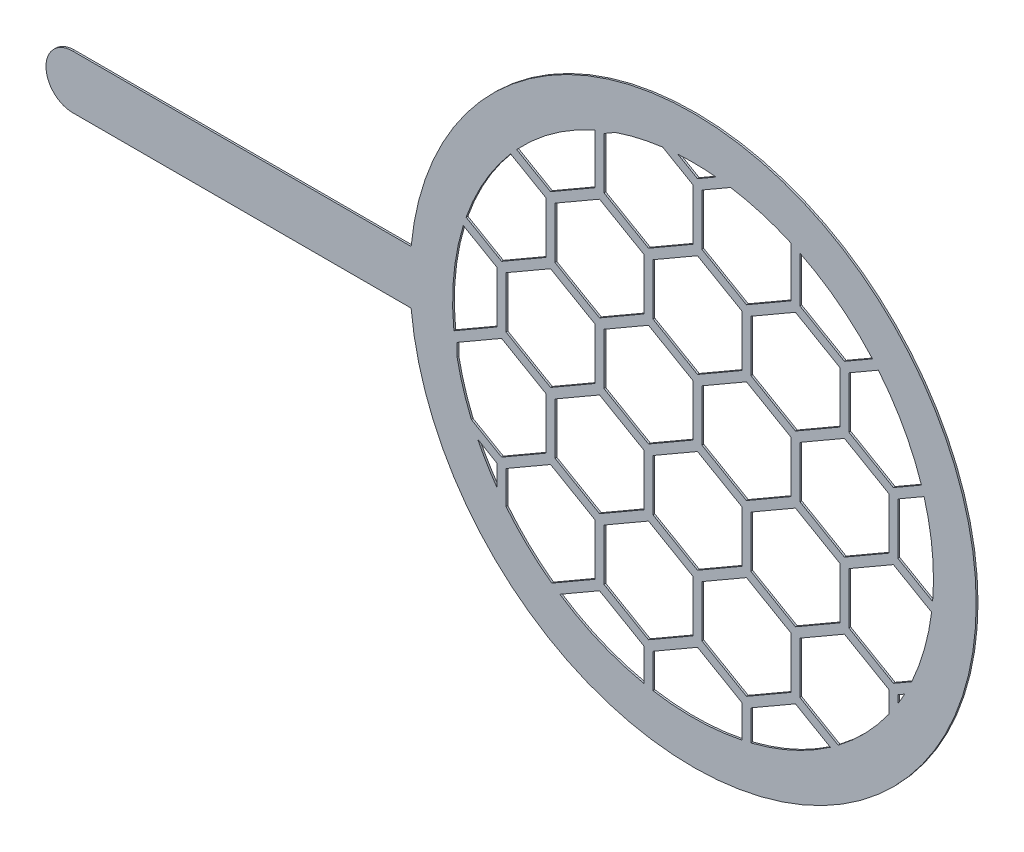
SolidWorks part; units mm, degrees
ref_plane "Plan de face" through (0, 0, 0) normal (0, 0, 1) x (1, 0, 0)
ref_plane "Plan de dessus" through (0, 0, 0) normal (0, 1, 0) x (1, 0, 0)
ref_plane "Plan de droite" through (0, 0, 0) normal (1, 0, 0) x (0, 0, -1)
sketch "Esquisse1" plane through (0, 0, 0) normal (0, 0, 1) x (1, 0, 0)
  line L0 (8, -1.4434) -> (8, 1.4434)
  line L1 (2.5, -1.4434) -> (2.5, 1.4434)
  line L2 (2.5, 1.4434) -> (0, 2.8868)
  line L3 (0, 2.8868) -> (-2.5, 1.4434)
  line L4 (-2.5, 1.4434) -> (-2.5, -1.4434)
  line L5 (-2.5, -1.4434) -> (0, -2.8868)
  line L6 (0, -2.8868) -> (2.5, -1.4434)
  line L7 (5.25, -6.2065) -> (5.25, -3.3198)
  line L8 (5.25, -3.3198) -> (2.75, -1.8764)
  line L9 (2.75, -1.8764) -> (0.25, -3.3198)
  line L10 (0.25, -3.3198) -> (0.25, -6.2065)
  line L11 (0.25, -6.2065) -> (2.75, -7.6499)
  line L12 (2.75, -7.6499) -> (5.25, -6.2065)
  line L13 (8, 1.4434) -> (5.5, 2.8868)
  line L14 (5.5, 2.8868) -> (3, 1.4434)
  line L15 (3, 1.4434) -> (3, -1.4434)
  line L16 (3, -1.4434) -> (5.5, -2.8868)
  line L17 (5.5, -2.8868) -> (8, -1.4434)
  line L18 (10.75, -6.2065) -> (10.75, -3.3198)
  line L19 (10.75, -3.3198) -> (8.25, -1.8764)
  line L20 (8.25, -1.8764) -> (5.75, -3.3198)
  line L21 (5.75, -3.3198) -> (5.75, -6.2065)
  line L22 (5.75, -6.2065) -> (8.25, -7.6499)
  line L23 (8.25, -7.6499) -> (10.75, -6.2065)
  line L24 (13.5, -1.4434) -> (13.5, 1.4434)
  line L25 (13.5, 1.4434) -> (11, 2.8868)
  line L26 (11, 2.8868) -> (8.5, 1.4434)
  line L27 (8.5, 1.4434) -> (8.5, -1.4434)
  line L28 (8.5, -1.4434) -> (11, -2.8868)
  line L29 (11, -2.8868) -> (13.5, -1.4434)
  line L30 (16.25, -6.2065) -> (16.25, -3.3198)
  line L31 (16.25, -3.3198) -> (13.75, -1.8764)
  line L32 (13.75, -1.8764) -> (11.25, -3.3198)
  line L33 (11.25, -3.3198) -> (11.25, -6.2065)
  line L34 (11.25, -6.2065) -> (13.75, -7.6499)
  line L35 (13.75, -7.6499) -> (16.25, -6.2065)
  line L36 (19, -1.4434) -> (19, 1.4434)
  line L37 (19, 1.4434) -> (16.5, 2.8868)
  line L38 (16.5, 2.8868) -> (14, 1.4434)
  line L39 (14, 1.4434) -> (14, -1.4434)
  line L40 (14, -1.4434) -> (16.5, -2.8868)
  line L41 (16.5, -2.8868) -> (19, -1.4434)
  line L42 (21.75, -6.2065) -> (21.75, -3.3198)
  line L43 (21.75, -3.3198) -> (19.25, -1.8764)
  line L44 (19.25, -1.8764) -> (16.75, -3.3198)
  line L45 (16.75, -3.3198) -> (16.75, -6.2065)
  line L46 (16.75, -6.2065) -> (19.25, -7.6499)
  line L47 (19.25, -7.6499) -> (21.75, -6.2065)
  line L48 (24.5, -1.4434) -> (24.5, 1.4434)
  line L49 (24.5, 1.4434) -> (22, 2.8868)
  line L50 (22, 2.8868) -> (19.5, 1.4434)
  line L51 (19.5, 1.4434) -> (19.5, -1.4434)
  line L52 (19.5, -1.4434) -> (22, -2.8868)
  line L53 (22, -2.8868) -> (24.5, -1.4434)
  line L54 (27.25, -6.2065) -> (27.25, -3.3198)
  line L55 (27.25, -3.3198) -> (24.75, -1.8764)
  line L56 (24.75, -1.8764) -> (22.25, -3.3198)
  line L57 (22.25, -3.3198) -> (22.25, -6.2065)
  line L58 (22.25, -6.2065) -> (24.75, -7.6499)
  line L59 (24.75, -7.6499) -> (27.25, -6.2065)
  line L60 (30, -1.4434) -> (30, 1.4434)
  line L61 (30, 1.4434) -> (27.5, 2.8868)
  line L62 (27.5, 2.8868) -> (25, 1.4434)
  line L63 (25, 1.4434) -> (25, -1.4434)
  line L64 (25, -1.4434) -> (27.5, -2.8868)
  line L65 (27.5, -2.8868) -> (30, -1.4434)
  line L66 (32.75, -6.2065) -> (32.75, -3.3198)
  line L67 (32.75, -3.3198) -> (30.25, -1.8764)
  line L68 (30.25, -1.8764) -> (27.75, -3.3198)
  line L69 (27.75, -3.3198) -> (27.75, -6.2065)
  line L70 (27.75, -6.2065) -> (30.25, -7.6499)
  line L71 (30.25, -7.6499) -> (32.75, -6.2065)
  line L72 (35.5, -1.4434) -> (35.5, 1.4434)
  line L73 (35.5, 1.4434) -> (33, 2.8868)
  line L74 (33, 2.8868) -> (30.5, 1.4434)
  line L75 (30.5, 1.4434) -> (30.5, -1.4434)
  line L76 (30.5, -1.4434) -> (33, -2.8868)
  line L77 (33, -2.8868) -> (35.5, -1.4434)
  line L78 (38.25, -6.2065) -> (38.25, -3.3198)
  line L79 (38.25, -3.3198) -> (35.75, -1.8764)
  line L80 (35.75, -1.8764) -> (33.25, -3.3198)
  line L81 (33.25, -3.3198) -> (33.25, -6.2065)
  line L82 (33.25, -6.2065) -> (35.75, -7.6499)
  line L83 (35.75, -7.6499) -> (38.25, -6.2065)
  line L84 (41, -1.4434) -> (41, 1.4434)
  line L85 (41, 1.4434) -> (38.5, 2.8868)
  line L86 (38.5, 2.8868) -> (36, 1.4434)
  line L87 (36, 1.4434) -> (36, -1.4434)
  line L88 (36, -1.4434) -> (38.5, -2.8868)
  line L89 (38.5, -2.8868) -> (41, -1.4434)
  line L90 (43.75, -6.2065) -> (43.75, -3.3198)
  line L91 (43.75, -3.3198) -> (41.25, -1.8764)
  line L92 (41.25, -1.8764) -> (38.75, -3.3198)
  line L93 (38.75, -3.3198) -> (38.75, -6.2065)
  line L94 (38.75, -6.2065) -> (41.25, -7.6499)
  line L95 (41.25, -7.6499) -> (43.75, -6.2065)
  line L96 (8, 8.0766) -> (8, 10.9634)
  line L97 (8, 10.9634) -> (5.5, 12.4068)
  line L98 (5.5, 12.4068) -> (3, 10.9634)
  line L99 (3, 10.9634) -> (3, 8.0766)
  line L100 (3, 8.0766) -> (5.5, 6.6332)
  line L101 (5.5, 6.6332) -> (8, 8.0766)
  line L102 (10.75, 3.3135) -> (10.75, 6.2002)
  line L103 (10.75, 6.2002) -> (8.25, 7.6436)
  line L104 (8.25, 7.6436) -> (5.75, 6.2002)
  line L105 (5.75, 6.2002) -> (5.75, 3.3135)
  line L106 (5.75, 3.3135) -> (8.25, 1.8701)
  line L107 (8.25, 1.8701) -> (10.75, 3.3135)
  line L108 (13.5, 8.0766) -> (13.5, 10.9634)
  line L109 (13.5, 10.9634) -> (11, 12.4068)
  line L110 (11, 12.4068) -> (8.5, 10.9634)
  line L111 (8.5, 10.9634) -> (8.5, 8.0766)
  line L112 (8.5, 8.0766) -> (11, 6.6332)
  line L113 (11, 6.6332) -> (13.5, 8.0766)
  line L114 (16.25, 3.3135) -> (16.25, 6.2002)
  line L115 (16.25, 6.2002) -> (13.75, 7.6436)
  line L116 (13.75, 7.6436) -> (11.25, 6.2002)
  line L117 (11.25, 6.2002) -> (11.25, 3.3135)
  line L118 (11.25, 3.3135) -> (13.75, 1.8701)
  line L119 (13.75, 1.8701) -> (16.25, 3.3135)
  line L120 (19, 8.0766) -> (19, 10.9634)
  line L121 (19, 10.9634) -> (16.5, 12.4068)
  line L122 (16.5, 12.4068) -> (14, 10.9634)
  line L123 (14, 10.9634) -> (14, 8.0766)
  line L124 (14, 8.0766) -> (16.5, 6.6332)
  line L125 (16.5, 6.6332) -> (19, 8.0766)
  line L126 (21.75, 3.3135) -> (21.75, 6.2002)
  line L127 (21.75, 6.2002) -> (19.25, 7.6436)
  line L128 (19.25, 7.6436) -> (16.75, 6.2002)
  line L129 (16.75, 6.2002) -> (16.75, 3.3135)
  line L130 (16.75, 3.3135) -> (19.25, 1.8701)
  line L131 (19.25, 1.8701) -> (21.75, 3.3135)
  line L132 (24.5, 8.0766) -> (24.5, 10.9634)
  line L133 (24.5, 10.9634) -> (22, 12.4068)
  line L134 (22, 12.4068) -> (19.5, 10.9634)
  line L135 (19.5, 10.9634) -> (19.5, 8.0766)
  line L136 (19.5, 8.0766) -> (22, 6.6332)
  line L137 (22, 6.6332) -> (24.5, 8.0766)
  line L138 (27.25, 3.3135) -> (27.25, 6.2002)
  line L139 (27.25, 6.2002) -> (24.75, 7.6436)
  line L140 (24.75, 7.6436) -> (22.25, 6.2002)
  line L141 (22.25, 6.2002) -> (22.25, 3.3135)
  line L142 (22.25, 3.3135) -> (24.75, 1.8701)
  line L143 (24.75, 1.8701) -> (27.25, 3.3135)
  line L144 (30, 8.0766) -> (30, 10.9634)
  line L145 (30, 10.9634) -> (27.5, 12.4068)
  line L146 (27.5, 12.4068) -> (25, 10.9634)
  line L147 (25, 10.9634) -> (25, 8.0766)
  line L148 (25, 8.0766) -> (27.5, 6.6332)
  line L149 (27.5, 6.6332) -> (30, 8.0766)
  line L150 (32.75, 3.3135) -> (32.75, 6.2002)
  line L151 (32.75, 6.2002) -> (30.25, 7.6436)
  line L152 (30.25, 7.6436) -> (27.75, 6.2002)
  line L153 (27.75, 6.2002) -> (27.75, 3.3135)
  line L154 (27.75, 3.3135) -> (30.25, 1.8701)
  line L155 (30.25, 1.8701) -> (32.75, 3.3135)
  line L156 (35.5, 8.0766) -> (35.5, 10.9634)
  line L157 (35.5, 10.9634) -> (33, 12.4068)
  line L158 (33, 12.4068) -> (30.5, 10.9634)
  line L159 (30.5, 10.9634) -> (30.5, 8.0766)
  line L160 (30.5, 8.0766) -> (33, 6.6332)
  line L161 (33, 6.6332) -> (35.5, 8.0766)
  line L162 (38.25, 3.3135) -> (38.25, 6.2002)
  line L163 (38.25, 6.2002) -> (35.75, 7.6436)
  line L164 (35.75, 7.6436) -> (33.25, 6.2002)
  line L165 (33.25, 6.2002) -> (33.25, 3.3135)
  line L166 (33.25, 3.3135) -> (35.75, 1.8701)
  line L167 (35.75, 1.8701) -> (38.25, 3.3135)
  line L168 (41, 8.0766) -> (41, 10.9634)
  line L169 (41, 10.9634) -> (38.5, 12.4068)
  line L170 (38.5, 12.4068) -> (36, 10.9634)
  line L171 (36, 10.9634) -> (36, 8.0766)
  line L172 (36, 8.0766) -> (38.5, 6.6332)
  line L173 (38.5, 6.6332) -> (41, 8.0766)
  line L174 (43.75, 3.3135) -> (43.75, 6.2002)
  line L175 (43.75, 6.2002) -> (41.25, 7.6436)
  line L176 (41.25, 7.6436) -> (38.75, 6.2002)
  line L177 (38.75, 6.2002) -> (38.75, 3.3135)
  line L178 (38.75, 3.3135) -> (41.25, 1.8701)
  line L179 (41.25, 1.8701) -> (43.75, 3.3135)
  line L180 (8, 17.5966) -> (8, 20.4834)
  line L181 (8, 20.4834) -> (5.5, 21.9268)
  line L182 (5.5, 21.9268) -> (3, 20.4834)
  line L183 (3, 20.4834) -> (3, 17.5966)
  line L184 (3, 17.5966) -> (5.5, 16.1532)
  line L185 (5.5, 16.1532) -> (8, 17.5966)
  line L186 (10.75, 12.8335) -> (10.75, 15.7202)
  line L187 (10.75, 15.7202) -> (8.25, 17.1636)
  line L188 (8.25, 17.1636) -> (5.75, 15.7202)
  line L189 (5.75, 15.7202) -> (5.75, 12.8335)
  line L190 (5.75, 12.8335) -> (8.25, 11.3901)
  line L191 (8.25, 11.3901) -> (10.75, 12.8335)
  line L192 (13.5, 17.5966) -> (13.5, 20.4834)
  line L193 (13.5, 20.4834) -> (11, 21.9268)
  line L194 (11, 21.9268) -> (8.5, 20.4834)
  line L195 (8.5, 20.4834) -> (8.5, 17.5966)
  line L196 (8.5, 17.5966) -> (11, 16.1532)
  line L197 (11, 16.1532) -> (13.5, 17.5966)
  line L198 (16.25, 12.8335) -> (16.25, 15.7202)
  line L199 (16.25, 15.7202) -> (13.75, 17.1636)
  line L200 (13.75, 17.1636) -> (11.25, 15.7202)
  line L201 (11.25, 15.7202) -> (11.25, 12.8335)
  line L202 (11.25, 12.8335) -> (13.75, 11.3901)
  line L203 (13.75, 11.3901) -> (16.25, 12.8335)
  line L204 (19, 17.5966) -> (19, 20.4834)
  line L205 (19, 20.4834) -> (16.5, 21.9268)
  line L206 (16.5, 21.9268) -> (14, 20.4834)
  line L207 (14, 20.4834) -> (14, 17.5966)
  line L208 (14, 17.5966) -> (16.5, 16.1532)
  line L209 (16.5, 16.1532) -> (19, 17.5966)
  line L210 (21.75, 12.8335) -> (21.75, 15.7202)
  line L211 (21.75, 15.7202) -> (19.25, 17.1636)
  line L212 (19.25, 17.1636) -> (16.75, 15.7202)
  line L213 (16.75, 15.7202) -> (16.75, 12.8335)
  line L214 (16.75, 12.8335) -> (19.25, 11.3901)
  line L215 (19.25, 11.3901) -> (21.75, 12.8335)
  line L216 (24.5, 17.5966) -> (24.5, 20.4834)
  line L217 (24.5, 20.4834) -> (22, 21.9268)
  line L218 (22, 21.9268) -> (19.5, 20.4834)
  line L219 (19.5, 20.4834) -> (19.5, 17.5966)
  line L220 (19.5, 17.5966) -> (22, 16.1532)
  line L221 (22, 16.1532) -> (24.5, 17.5966)
  line L222 (27.25, 12.8335) -> (27.25, 15.7202)
  line L223 (27.25, 15.7202) -> (24.75, 17.1636)
  line L224 (24.75, 17.1636) -> (22.25, 15.7202)
  line L225 (22.25, 15.7202) -> (22.25, 12.8335)
  line L226 (22.25, 12.8335) -> (24.75, 11.3901)
  line L227 (24.75, 11.3901) -> (27.25, 12.8335)
  line L228 (30, 17.5966) -> (30, 20.4834)
  line L229 (30, 20.4834) -> (27.5, 21.9268)
  line L230 (27.5, 21.9268) -> (25, 20.4834)
  line L231 (25, 20.4834) -> (25, 17.5966)
  line L232 (25, 17.5966) -> (27.5, 16.1532)
  line L233 (27.5, 16.1532) -> (30, 17.5966)
  line L234 (32.75, 12.8335) -> (32.75, 15.7202)
  line L235 (32.75, 15.7202) -> (30.25, 17.1636)
  line L236 (30.25, 17.1636) -> (27.75, 15.7202)
  line L237 (27.75, 15.7202) -> (27.75, 12.8335)
  line L238 (27.75, 12.8335) -> (30.25, 11.3901)
  line L239 (30.25, 11.3901) -> (32.75, 12.8335)
  line L240 (35.5, 17.5966) -> (35.5, 20.4834)
  line L241 (35.5, 20.4834) -> (33, 21.9268)
  line L242 (33, 21.9268) -> (30.5, 20.4834)
  line L243 (30.5, 20.4834) -> (30.5, 17.5966)
  line L244 (30.5, 17.5966) -> (33, 16.1532)
  line L245 (33, 16.1532) -> (35.5, 17.5966)
  line L246 (38.25, 12.8335) -> (38.25, 15.7202)
  line L247 (38.25, 15.7202) -> (35.75, 17.1636)
  line L248 (35.75, 17.1636) -> (33.25, 15.7202)
  line L249 (33.25, 15.7202) -> (33.25, 12.8335)
  line L250 (33.25, 12.8335) -> (35.75, 11.3901)
  line L251 (35.75, 11.3901) -> (38.25, 12.8335)
  line L252 (41, 17.5966) -> (41, 20.4834)
  line L253 (41, 20.4834) -> (38.5, 21.9268)
  line L254 (38.5, 21.9268) -> (36, 20.4834)
  line L255 (36, 20.4834) -> (36, 17.5966)
  line L256 (36, 17.5966) -> (38.5, 16.1532)
  line L257 (38.5, 16.1532) -> (41, 17.5966)
  line L258 (43.75, 12.8335) -> (43.75, 15.7202)
  line L259 (43.75, 15.7202) -> (41.25, 17.1636)
  line L260 (41.25, 17.1636) -> (38.75, 15.7202)
  line L261 (38.75, 15.7202) -> (38.75, 12.8335)
  line L262 (38.75, 12.8335) -> (41.25, 11.3901)
  line L263 (41.25, 11.3901) -> (43.75, 12.8335)
  line L264 (8, 27.1166) -> (8, 30.0034)
  line L265 (8, 30.0034) -> (5.5, 31.4468)
  line L266 (5.5, 31.4468) -> (3, 30.0034)
  line L267 (3, 30.0034) -> (3, 27.1166)
  line L268 (3, 27.1166) -> (5.5, 25.6732)
  line L269 (5.5, 25.6732) -> (8, 27.1166)
  line L270 (10.75, 22.3535) -> (10.75, 25.2402)
  line L271 (10.75, 25.2402) -> (8.25, 26.6836)
  line L272 (8.25, 26.6836) -> (5.75, 25.2402)
  line L273 (5.75, 25.2402) -> (5.75, 22.3535)
  line L274 (5.75, 22.3535) -> (8.25, 20.9101)
  line L275 (8.25, 20.9101) -> (10.75, 22.3535)
  line L276 (13.5, 27.1166) -> (13.5, 30.0034)
  line L277 (13.5, 30.0034) -> (11, 31.4468)
  line L278 (11, 31.4468) -> (8.5, 30.0034)
  line L279 (8.5, 30.0034) -> (8.5, 27.1166)
  line L280 (8.5, 27.1166) -> (11, 25.6732)
  line L281 (11, 25.6732) -> (13.5, 27.1166)
  line L282 (16.25, 22.3535) -> (16.25, 25.2402)
  line L283 (16.25, 25.2402) -> (13.75, 26.6836)
  line L284 (13.75, 26.6836) -> (11.25, 25.2402)
  line L285 (11.25, 25.2402) -> (11.25, 22.3535)
  line L286 (11.25, 22.3535) -> (13.75, 20.9101)
  line L287 (13.75, 20.9101) -> (16.25, 22.3535)
  line L288 (19, 27.1166) -> (19, 30.0034)
  line L289 (19, 30.0034) -> (16.5, 31.4468)
  line L290 (16.5, 31.4468) -> (14, 30.0034)
  line L291 (14, 30.0034) -> (14, 27.1166)
  line L292 (14, 27.1166) -> (16.5, 25.6732)
  line L293 (16.5, 25.6732) -> (19, 27.1166)
  line L294 (21.75, 22.3535) -> (21.75, 25.2402)
  line L295 (21.75, 25.2402) -> (19.25, 26.6836)
  line L296 (19.25, 26.6836) -> (16.75, 25.2402)
  line L297 (16.75, 25.2402) -> (16.75, 22.3535)
  line L298 (16.75, 22.3535) -> (19.25, 20.9101)
  line L299 (19.25, 20.9101) -> (21.75, 22.3535)
  line L300 (24.5, 27.1166) -> (24.5, 30.0034)
  line L301 (24.5, 30.0034) -> (22, 31.4468)
  line L302 (22, 31.4468) -> (19.5, 30.0034)
  line L303 (19.5, 30.0034) -> (19.5, 27.1166)
  line L304 (19.5, 27.1166) -> (22, 25.6732)
  line L305 (22, 25.6732) -> (24.5, 27.1166)
  line L306 (27.25, 22.3535) -> (27.25, 25.2402)
  line L307 (27.25, 25.2402) -> (24.75, 26.6836)
  line L308 (24.75, 26.6836) -> (22.25, 25.2402)
  line L309 (22.25, 25.2402) -> (22.25, 22.3535)
  line L310 (22.25, 22.3535) -> (24.75, 20.9101)
  line L311 (24.75, 20.9101) -> (27.25, 22.3535)
  line L312 (30, 27.1166) -> (30, 30.0034)
  line L313 (30, 30.0034) -> (27.5, 31.4468)
  line L314 (27.5, 31.4468) -> (25, 30.0034)
  line L315 (25, 30.0034) -> (25, 27.1166)
  line L316 (25, 27.1166) -> (27.5, 25.6732)
  line L317 (27.5, 25.6732) -> (30, 27.1166)
  line L318 (32.75, 22.3535) -> (32.75, 25.2402)
  line L319 (32.75, 25.2402) -> (30.25, 26.6836)
  line L320 (30.25, 26.6836) -> (27.75, 25.2402)
  line L321 (27.75, 25.2402) -> (27.75, 22.3535)
  line L322 (27.75, 22.3535) -> (30.25, 20.9101)
  line L323 (30.25, 20.9101) -> (32.75, 22.3535)
  line L324 (35.5, 27.1166) -> (35.5, 30.0034)
  line L325 (35.5, 30.0034) -> (33, 31.4468)
  line L326 (33, 31.4468) -> (30.5, 30.0034)
  line L327 (30.5, 30.0034) -> (30.5, 27.1166)
  line L328 (30.5, 27.1166) -> (33, 25.6732)
  line L329 (33, 25.6732) -> (35.5, 27.1166)
  line L330 (38.25, 22.3535) -> (38.25, 25.2402)
  line L331 (38.25, 25.2402) -> (35.75, 26.6836)
  line L332 (35.75, 26.6836) -> (33.25, 25.2402)
  line L333 (33.25, 25.2402) -> (33.25, 22.3535)
  line L334 (33.25, 22.3535) -> (35.75, 20.9101)
  line L335 (35.75, 20.9101) -> (38.25, 22.3535)
  line L336 (41, 27.1166) -> (41, 30.0034)
  line L337 (41, 30.0034) -> (38.5, 31.4468)
  line L338 (38.5, 31.4468) -> (36, 30.0034)
  line L339 (36, 30.0034) -> (36, 27.1166)
  line L340 (36, 27.1166) -> (38.5, 25.6732)
  line L341 (38.5, 25.6732) -> (41, 27.1166)
  line L342 (43.75, 22.3535) -> (43.75, 25.2402)
  line L343 (43.75, 25.2402) -> (41.25, 26.6836)
  line L344 (41.25, 26.6836) -> (38.75, 25.2402)
  line L345 (38.75, 25.2402) -> (38.75, 22.3535)
  line L346 (38.75, 22.3535) -> (41.25, 20.9101)
  line L347 (41.25, 20.9101) -> (43.75, 22.3535)
  line L348 (8, 36.6366) -> (8, 39.5234)
  line L349 (8, 39.5234) -> (5.5, 40.9668)
  line L350 (5.5, 40.9668) -> (3, 39.5234)
  line L351 (3, 39.5234) -> (3, 36.6366)
  line L352 (3, 36.6366) -> (5.5, 35.1932)
  line L353 (5.5, 35.1932) -> (8, 36.6366)
  line L354 (10.75, 31.8735) -> (10.75, 34.7602)
  line L355 (10.75, 34.7602) -> (8.25, 36.2036)
  line L356 (8.25, 36.2036) -> (5.75, 34.7602)
  line L357 (5.75, 34.7602) -> (5.75, 31.8735)
  line L358 (5.75, 31.8735) -> (8.25, 30.4301)
  line L359 (8.25, 30.4301) -> (10.75, 31.8735)
  line L360 (13.5, 36.6366) -> (13.5, 39.5234)
  line L361 (13.5, 39.5234) -> (11, 40.9668)
  line L362 (11, 40.9668) -> (8.5, 39.5234)
  line L363 (8.5, 39.5234) -> (8.5, 36.6366)
  line L364 (8.5, 36.6366) -> (11, 35.1932)
  line L365 (11, 35.1932) -> (13.5, 36.6366)
  line L366 (16.25, 31.8735) -> (16.25, 34.7602)
  line L367 (16.25, 34.7602) -> (13.75, 36.2036)
  line L368 (13.75, 36.2036) -> (11.25, 34.7602)
  line L369 (11.25, 34.7602) -> (11.25, 31.8735)
  line L370 (11.25, 31.8735) -> (13.75, 30.4301)
  line L371 (13.75, 30.4301) -> (16.25, 31.8735)
  line L372 (19, 36.6366) -> (19, 39.5234)
  line L373 (19, 39.5234) -> (16.5, 40.9668)
  line L374 (16.5, 40.9668) -> (14, 39.5234)
  line L375 (14, 39.5234) -> (14, 36.6366)
  line L376 (14, 36.6366) -> (16.5, 35.1932)
  line L377 (16.5, 35.1932) -> (19, 36.6366)
  line L378 (21.75, 31.8735) -> (21.75, 34.7602)
  line L379 (21.75, 34.7602) -> (19.25, 36.2036)
  line L380 (19.25, 36.2036) -> (16.75, 34.7602)
  line L381 (16.75, 34.7602) -> (16.75, 31.8735)
  line L382 (16.75, 31.8735) -> (19.25, 30.4301)
  line L383 (19.25, 30.4301) -> (21.75, 31.8735)
  line L384 (24.5, 36.6366) -> (24.5, 39.5234)
  line L385 (24.5, 39.5234) -> (22, 40.9668)
  line L386 (22, 40.9668) -> (19.5, 39.5234)
  line L387 (19.5, 39.5234) -> (19.5, 36.6366)
  line L388 (19.5, 36.6366) -> (22, 35.1932)
  line L389 (22, 35.1932) -> (24.5, 36.6366)
  line L390 (27.25, 31.8735) -> (27.25, 34.7602)
  line L391 (27.25, 34.7602) -> (24.75, 36.2036)
  line L392 (24.75, 36.2036) -> (22.25, 34.7602)
  line L393 (22.25, 34.7602) -> (22.25, 31.8735)
  line L394 (22.25, 31.8735) -> (24.75, 30.4301)
  line L395 (24.75, 30.4301) -> (27.25, 31.8735)
  line L396 (30, 36.6366) -> (30, 39.5234)
  line L397 (30, 39.5234) -> (27.5, 40.9668)
  line L398 (27.5, 40.9668) -> (25, 39.5234)
  line L399 (25, 39.5234) -> (25, 36.6366)
  line L400 (25, 36.6366) -> (27.5, 35.1932)
  line L401 (27.5, 35.1932) -> (30, 36.6366)
  line L402 (32.75, 31.8735) -> (32.75, 34.7602)
  line L403 (32.75, 34.7602) -> (30.25, 36.2036)
  line L404 (30.25, 36.2036) -> (27.75, 34.7602)
  line L405 (27.75, 34.7602) -> (27.75, 31.8735)
  line L406 (27.75, 31.8735) -> (30.25, 30.4301)
  line L407 (30.25, 30.4301) -> (32.75, 31.8735)
  line L408 (35.5, 36.6366) -> (35.5, 39.5234)
  line L409 (35.5, 39.5234) -> (33, 40.9668)
  line L410 (33, 40.9668) -> (30.5, 39.5234)
  line L411 (30.5, 39.5234) -> (30.5, 36.6366)
  line L412 (30.5, 36.6366) -> (33, 35.1932)
  line L413 (33, 35.1932) -> (35.5, 36.6366)
  line L414 (38.25, 31.8735) -> (38.25, 34.7602)
  line L415 (38.25, 34.7602) -> (35.75, 36.2036)
  line L416 (35.75, 36.2036) -> (33.25, 34.7602)
  line L417 (33.25, 34.7602) -> (33.25, 31.8735)
  line L418 (33.25, 31.8735) -> (35.75, 30.4301)
  line L419 (35.75, 30.4301) -> (38.25, 31.8735)
  line L420 (41, 36.6366) -> (41, 39.5234)
  line L421 (41, 39.5234) -> (38.5, 40.9668)
  line L422 (38.5, 40.9668) -> (36, 39.5234)
  line L423 (36, 39.5234) -> (36, 36.6366)
  line L424 (36, 36.6366) -> (38.5, 35.1932)
  line L425 (38.5, 35.1932) -> (41, 36.6366)
  line L426 (43.75, 31.8735) -> (43.75, 34.7602)
  line L427 (43.75, 34.7602) -> (41.25, 36.2036)
  line L428 (41.25, 36.2036) -> (38.75, 34.7602)
  line L429 (38.75, 34.7602) -> (38.75, 31.8735)
  line L430 (38.75, 31.8735) -> (41.25, 30.4301)
  line L431 (41.25, 30.4301) -> (43.75, 31.8735)
  line L432 (2.5, 8.0766) -> (2.5, 10.9634)
  line L433 (2.5, 10.9634) -> (0, 12.4068)
  line L434 (0, 12.4068) -> (-2.5, 10.9634)
  line L435 (-2.5, 10.9634) -> (-2.5, 8.0766)
  line L436 (-2.5, 8.0766) -> (0, 6.6332)
  line L437 (0, 6.6332) -> (2.5, 8.0766)
  line L438 (5.25, 3.3135) -> (5.25, 6.2002)
  line L439 (5.25, 6.2002) -> (2.75, 7.6436)
  line L440 (2.75, 7.6436) -> (0.25, 6.2002)
  line L441 (0.25, 6.2002) -> (0.25, 3.3135)
  line L442 (0.25, 3.3135) -> (2.75, 1.8701)
  line L443 (2.75, 1.8701) -> (5.25, 3.3135)
  line L444 (2.5, 17.5966) -> (2.5, 20.4834)
  line L445 (2.5, 20.4834) -> (0, 21.9268)
  line L446 (0, 21.9268) -> (-2.5, 20.4834)
  line L447 (-2.5, 20.4834) -> (-2.5, 17.5966)
  line L448 (-2.5, 17.5966) -> (0, 16.1532)
  line L449 (0, 16.1532) -> (2.5, 17.5966)
  line L450 (5.25, 12.8335) -> (5.25, 15.7202)
  line L451 (5.25, 15.7202) -> (2.75, 17.1636)
  line L452 (2.75, 17.1636) -> (0.25, 15.7202)
  line L453 (0.25, 15.7202) -> (0.25, 12.8335)
  line L454 (0.25, 12.8335) -> (2.75, 11.3901)
  line L455 (2.75, 11.3901) -> (5.25, 12.8335)
  line L456 (2.5, 27.1166) -> (2.5, 30.0034)
  line L457 (2.5, 30.0034) -> (0, 31.4468)
  line L458 (0, 31.4468) -> (-2.5, 30.0034)
  line L459 (-2.5, 30.0034) -> (-2.5, 27.1166)
  line L460 (-2.5, 27.1166) -> (0, 25.6732)
  line L461 (0, 25.6732) -> (2.5, 27.1166)
  line L462 (5.25, 22.3535) -> (5.25, 25.2402)
  line L463 (5.25, 25.2402) -> (2.75, 26.6836)
  line L464 (2.75, 26.6836) -> (0.25, 25.2402)
  line L465 (0.25, 25.2402) -> (0.25, 22.3535)
  line L466 (0.25, 22.3535) -> (2.75, 20.9101)
  line L467 (2.75, 20.9101) -> (5.25, 22.3535)
  line L468 (2.5, 36.6366) -> (2.5, 39.5234)
  line L469 (2.5, 39.5234) -> (0, 40.9668)
  line L470 (0, 40.9668) -> (-2.5, 39.5234)
  line L471 (-2.5, 39.5234) -> (-2.5, 36.6366)
  line L472 (-2.5, 36.6366) -> (0, 35.1932)
  line L473 (0, 35.1932) -> (2.5, 36.6366)
  line L474 (5.25, 31.8735) -> (5.25, 34.7602)
  line L475 (5.25, 34.7602) -> (2.75, 36.2036)
  line L476 (2.75, 36.2036) -> (0.25, 34.7602)
  line L477 (0.25, 34.7602) -> (0.25, 31.8735)
  line L478 (0.25, 31.8735) -> (2.75, 30.4301)
  line L479 (2.75, 30.4301) -> (5.25, 31.8735)
  circle A0 centre (0, 0) radius 2.5 construction
  circle A1 centre (2.75, -4.7631) radius 2.5 construction
  circle A2 centre (5.5, 0) radius 2.5 construction
  circle A3 centre (8.25, -4.7631) radius 2.5 construction
  circle A4 centre (11, 0) radius 2.5 construction
  circle A5 centre (13.75, -4.7631) radius 2.5 construction
  circle A6 centre (16.5, 0) radius 2.5 construction
  circle A7 centre (19.25, -4.7631) radius 2.5 construction
  circle A8 centre (22, 0) radius 2.5 construction
  circle A9 centre (24.75, -4.7631) radius 2.5 construction
  circle A10 centre (27.5, 0) radius 2.5 construction
  circle A11 centre (30.25, -4.7631) radius 2.5 construction
  circle A12 centre (33, 0) radius 2.5 construction
  circle A13 centre (35.75, -4.7631) radius 2.5 construction
  circle A14 centre (38.5, 0) radius 2.5 construction
  circle A15 centre (41.25, -4.7631) radius 2.5 construction
  circle A16 centre (5.5, 9.52) radius 2.5 construction
  circle A17 centre (8.25, 4.7569) radius 2.5 construction
  circle A18 centre (11, 9.52) radius 2.5 construction
  circle A19 centre (13.75, 4.7569) radius 2.5 construction
  circle A20 centre (16.5, 9.52) radius 2.5 construction
  circle A21 centre (19.25, 4.7569) radius 2.5 construction
  circle A22 centre (22, 9.52) radius 2.5 construction
  circle A23 centre (24.75, 4.7569) radius 2.5 construction
  circle A24 centre (27.5, 9.52) radius 2.5 construction
  circle A25 centre (30.25, 4.7569) radius 2.5 construction
  circle A26 centre (33, 9.52) radius 2.5 construction
  circle A27 centre (35.75, 4.7569) radius 2.5 construction
  circle A28 centre (38.5, 9.52) radius 2.5 construction
  circle A29 centre (41.25, 4.7569) radius 2.5 construction
  circle A30 centre (5.5, 19.04) radius 2.5 construction
  circle A31 centre (8.25, 14.2769) radius 2.5 construction
  circle A32 centre (11, 19.04) radius 2.5 construction
  circle A33 centre (13.75, 14.2769) radius 2.5 construction
  circle A34 centre (16.5, 19.04) radius 2.5 construction
  circle A35 centre (19.25, 14.2769) radius 2.5 construction
  circle A36 centre (22, 19.04) radius 2.5 construction
  circle A37 centre (24.75, 14.2769) radius 2.5 construction
  circle A38 centre (27.5, 19.04) radius 2.5 construction
  circle A39 centre (30.25, 14.2769) radius 2.5 construction
  circle A40 centre (33, 19.04) radius 2.5 construction
  circle A41 centre (35.75, 14.2769) radius 2.5 construction
  circle A42 centre (38.5, 19.04) radius 2.5 construction
  circle A43 centre (41.25, 14.2769) radius 2.5 construction
  circle A44 centre (5.5, 28.56) radius 2.5 construction
  circle A45 centre (8.25, 23.7969) radius 2.5 construction
  circle A46 centre (11, 28.56) radius 2.5 construction
  circle A47 centre (13.75, 23.7969) radius 2.5 construction
  circle A48 centre (16.5, 28.56) radius 2.5 construction
  circle A49 centre (19.25, 23.7969) radius 2.5 construction
  circle A50 centre (22, 28.56) radius 2.5 construction
  circle A51 centre (24.75, 23.7969) radius 2.5 construction
  circle A52 centre (27.5, 28.56) radius 2.5 construction
  circle A53 centre (30.25, 23.7969) radius 2.5 construction
  circle A54 centre (33, 28.56) radius 2.5 construction
  circle A55 centre (35.75, 23.7969) radius 2.5 construction
  circle A56 centre (38.5, 28.56) radius 2.5 construction
  circle A57 centre (41.25, 23.7969) radius 2.5 construction
  circle A58 centre (5.5, 38.08) radius 2.5 construction
  circle A59 centre (8.25, 33.3169) radius 2.5 construction
  circle A60 centre (11, 38.08) radius 2.5 construction
  circle A61 centre (13.75, 33.3169) radius 2.5 construction
  circle A62 centre (16.5, 38.08) radius 2.5 construction
  circle A63 centre (19.25, 33.3169) radius 2.5 construction
  circle A64 centre (22, 38.08) radius 2.5 construction
  circle A65 centre (24.75, 33.3169) radius 2.5 construction
  circle A66 centre (27.5, 38.08) radius 2.5 construction
  circle A67 centre (30.25, 33.3169) radius 2.5 construction
  circle A68 centre (33, 38.08) radius 2.5 construction
  circle A69 centre (35.75, 33.3169) radius 2.5 construction
  circle A70 centre (38.5, 38.08) radius 2.5 construction
  circle A71 centre (41.25, 33.3169) radius 2.5 construction
  circle A72 centre (0, 9.52) radius 2.5 construction
  circle A73 centre (2.75, 4.7569) radius 2.5 construction
  circle A74 centre (0, 19.04) radius 2.5 construction
  circle A75 centre (2.75, 14.2769) radius 2.5 construction
  circle A76 centre (0, 28.56) radius 2.5 construction
  circle A77 centre (2.75, 23.7969) radius 2.5 construction
  circle A78 centre (0, 38.08) radius 2.5 construction
  circle A79 centre (2.75, 33.3169) radius 2.5 construction
  circle A80 centre (19, 17.5966) radius 13.5
  dimension "D9" = 27
  dimension "D1" = 5
  dimension "D2" = 5
  dimension "D3" = 0.5
  dimension "D4" = 0.25
  dimension "D5" = 9.0933
  dimension "D6" = 0.433
  dimension "D7" = 8
  dimension "D8" = 5
extrude "Boss.-Extru.1" add sketch "Esquisse1" along normal blind 0.1 contours L242 A80 L323 L322 L321 L320 L317 L316 L315 L300 L305 L304 L303 L302 L383 L382 L289 L288 L293 L292 L291 L290 L276 L281 L280 L271 L270 L275 L274 L181 L180 L185 L189 L188 L187 L186 L191 L190 L97 L96 L111 region at (19.0384, 17.5759, 0)
sketch "Esquisse2" plane through (0, 0, 0.1) normal (0, 0, 1) x (1, 0, 0)
  circle A0 centre (19, 17.5966) radius 15.9
  arc A1 (14.6413, 30.3736) -> (13.5, 29.9255) centre (19, 17.5966) ccw construction
  circle A2 centre (19, 17.5966) radius 13.5
  dimension "D1" = 31.8
  dimension "D2" = 27
extrude "Boss.-Extru.2" add sketch "Esquisse2" against normal blind 0.1
sketch "Esquisse3" plane through (0, 0, 0.1) normal (0, 0, 1) x (1, 0, 0)
  line L0 (34.9, 17.5966) -> (-10.4843, 17.5966) construction
  line L2 (-15.8291, 19.0966) -> (3.1709, 19.0966)
  line L3 (-15.8291, 19.0966) -> (-15.8291, 16.0966)
  line L4 (-15.8291, 16.0966) -> (3.1709, 16.0966)
  line L5 (3.1709, 19.0966) -> (3.1709, 16.0966)
  line L6 (-15.8291, 19.0966) -> (3.1709, 16.0966) construction
  line L7 (-15.8291, 16.0966) -> (3.1709, 19.0966) construction
  circle A0 centre (19, 17.5966) radius 15.9 construction
  point P5 (-6.3291, 17.5966)
  point P10 (0, 0)
  dimension "D1" = 19
  dimension "D2" = 3
extrude "Boss.-Extru.3" add sketch "Esquisse3" against normal blind 0.1
sketch "Esquisse4" plane through (0, 0, 0.1) normal (0, 0, 1) x (1, 0, 0)
  line L1 (-15.8291, 19.0966) -> (-15.8291, 16.0966)
  arc A0 (-15.8291, 19.0966) -> (-15.8291, 16.0966) centre (-15.8291, 17.5966) ccw
  dimension "D1" = 1.5
extrude "Boss.-Extru.4" add sketch "Esquisse4" against normal blind 0.1
